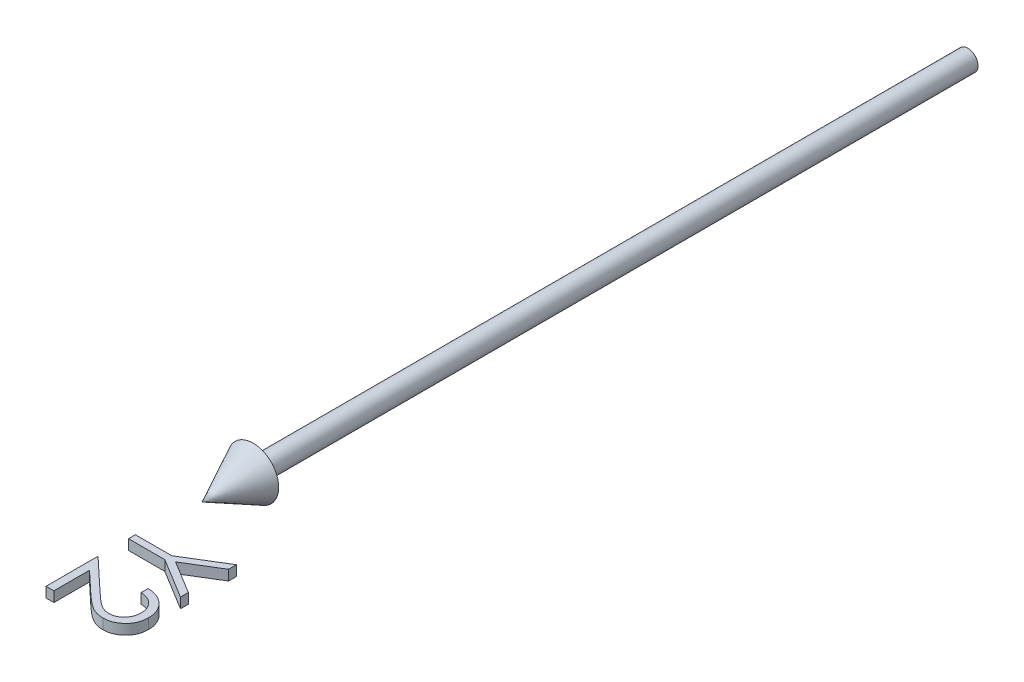
SolidWorks part; units mm, degrees
ref_plane "Front Plane" through (0, 0, 0) normal (0, 0, 1) x (1, 0, 0)
ref_plane "Top Plane" through (0, 0, 0) normal (0, 1, 0) x (1, 0, 0)
ref_plane "Right Plane" through (0, 0, 0) normal (1, 0, 0) x (0, 0, -1)
sketch "Sketch2" plane through (0, 0, 0) normal (0, 1, 0) x (1, 0, 0)
  line L0 (0, 41.95) -> (0, -114.4521) construction
  line L1 (-36.8894, 0) -> (41.4965, 0) construction
  line L2 (0, -150) -> (5, -140)
  line L3 (5, -140) -> (2, -140)
  line L4 (2, -140) -> (2, 0)
  line L5 (2, 0) -> (0, 0)
  line L6 (0, 0) -> (0, -150)
  dimension "D1" = 150
  dimension "D2" = 2
  dimension "D3" = 10
  dimension "D4" = 5
revolve "Revolve1" add sketch "Sketch2" angle 360 about L0
sketch "Sketch3" plane through (0, 0, 0) normal (0, 1, 0) x (1, 0, 0)
  line L0 (0, -157.5) -> (0, -275.0721) construction
  line L1 (-27.7611, 0) -> (48.5657, 0) construction
  text T0 "Y2\r\n" font "Century Gothic" height 15
  dimension "D1" = 157.5
extrude "Boss-Extrude1" add sketch "Sketch3" against normal blind 1 and the other way blind 1 separate body
equation "\"D1@Sketch2\"=\"frame_arrow_length\""
equation "\"D2@Sketch2\"=\"frame_arrow_odA\"/2"
equation "\"D4@Sketch2\"=\"frame_arrow_head_od\""
equation "\"D3@Sketch2\"=\"frame_arrow_head_length\""
equation "\"frame_arrow_length\"=150"
equation "\"frame_arrow_head_length\"=10"
equation "\"frame_arrow_head_od\"=5"
equation "\"frame_arrow_odA\"=4"
equation "\"D1@Sketch3\"=\"frame_arrow_length\"*1.05"
